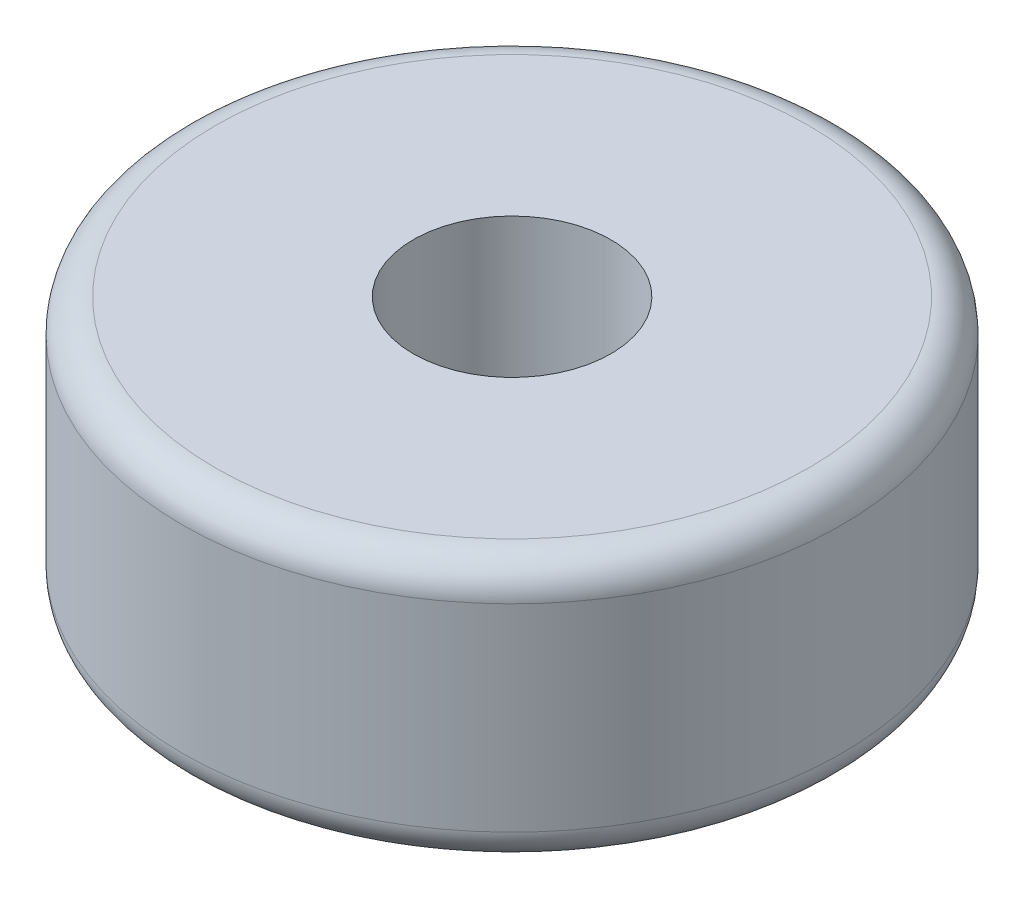
SolidWorks part; units mm, degrees
ref_plane "Front" through (0, 0, 0) normal (0, 0, 1) x (1, 0, 0)
ref_plane "Top" through (0, 0, 0) normal (0, 1, 0) x (1, 0, 0)
ref_plane "Right" through (0, 0, 0) normal (1, 0, 0) x (0, 0, -1)
sketch "Sketch1" plane through (0, 0, 0) normal (0, 1, 0) x (1, 0, 0)
  circle A0 centre (0, 0) radius 5
  circle A1 centre (0, 0) radius 1.5
  dimension "D1" = 10
  dimension "D2" = 3
extrude "Boss-Extrude1" add sketch "Sketch1" along normal blind 4
fillet "Fillet1" radius 0.5 2 edges at (0, 0, 5) (0, 4, 5)
